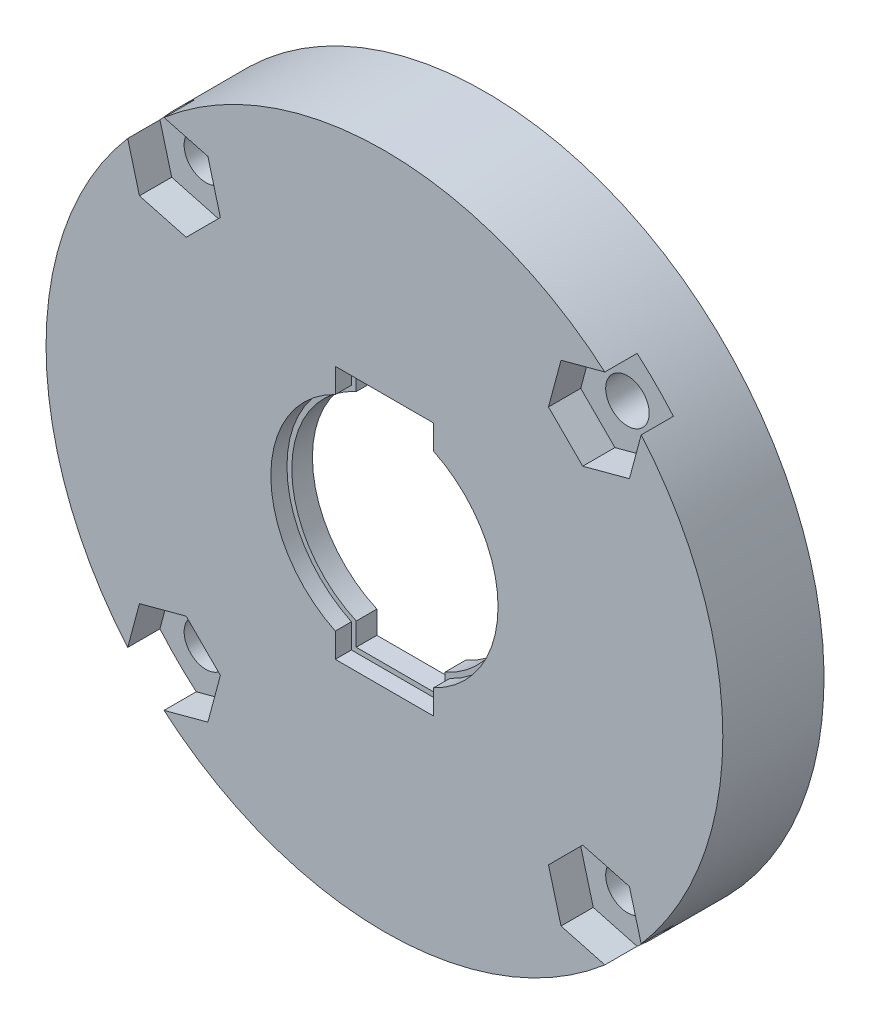
SolidWorks part; units mm, degrees
ref_plane "Front Plane" through (0, 0, 0) normal (0, 0, 1) x (1, 0, 0)
ref_plane "Top Plane" through (0, 0, 0) normal (0, 1, 0) x (1, 0, 0)
ref_plane "Right Plane" through (0, 0, 0) normal (1, 0, 0) x (0, 0, -1)
ref_axis "Z" through (0, 0, -0.1) along (0, 0, 1)
sketch "Sketch3" plane through (0, 0, 0) normal (0, 0, 1) x (1, 0, 0)
  line L132 (3.05, 6.3548) -> (3.05, 6.3561) construction
  line L133 (-3.05, 6.3561) -> (-3.05, 6.3548) construction
  line L134 (3.05, -6.3561) -> (3.05, -6.355) construction
  line L135 (-3.05, -6.355) -> (-3.05, -6.3561) construction
  line L198 (3.05, 6.3548) -> (3.05, 7.8744)
  line L199 (3.05, 7.8744) -> (-3.05, 7.8744)
  line L200 (-3.05, 7.8744) -> (-3.05, 6.3548)
  line L201 (-3.05, 6.3548) -> (-3.4914, 6.1247)
  line L202 (-3.4914, 6.1247) -> (-3.9416, 5.8451)
  line L203 (-3.9416, 5.8451) -> (-4.3696, 5.5325)
  line L204 (-4.3696, 5.5325) -> (-4.7729, 5.1886)
  line L205 (-4.7729, 5.1886) -> (-5.1492, 4.8154)
  line L206 (-5.1492, 4.8154) -> (-5.4964, 4.4149)
  line L207 (-5.4964, 4.4149) -> (-5.8125, 3.9896)
  line L208 (-5.8125, 3.9896) -> (-6.0958, 3.5417)
  line L209 (-6.0958, 3.5417) -> (-6.3446, 3.0737)
  line L210 (-6.3446, 3.0737) -> (-6.5576, 2.5884)
  line L211 (-6.5576, 2.5884) -> (-6.7335, 2.0885)
  line L212 (-6.7335, 2.0885) -> (-6.8714, 1.5768)
  line L213 (-6.8714, 1.5768) -> (-6.9705, 1.0561)
  line L214 (-6.9705, 1.0561) -> (-7.0301, 0.5295)
  line L215 (-7.0301, 0.5295) -> (-7.05, -0.0001)
  line L216 (-7.05, -0.0001) -> (-7.0301, -0.5297)
  line L217 (-7.0301, -0.5297) -> (-6.9705, -1.0563)
  line L218 (-6.9705, -1.0563) -> (-6.8714, -1.577)
  line L219 (-6.8714, -1.577) -> (-6.7335, -2.0887)
  line L220 (-6.7335, -2.0887) -> (-6.5576, -2.5887)
  line L221 (-6.5576, -2.5887) -> (-6.3446, -3.074)
  line L222 (-6.3446, -3.074) -> (-6.0958, -3.5419)
  line L223 (-6.0958, -3.5419) -> (-5.8125, -3.9898)
  line L224 (-5.8125, -3.9898) -> (-5.4964, -4.4152)
  line L225 (-5.4964, -4.4152) -> (-5.1492, -4.8156)
  line L226 (-5.1492, -4.8156) -> (-4.7729, -5.1888)
  line L227 (-4.7729, -5.1888) -> (-4.3696, -5.5327)
  line L228 (-4.3696, -5.5327) -> (-3.9416, -5.8453)
  line L229 (-3.9416, -5.8453) -> (-3.4914, -6.1249)
  line L230 (-3.4914, -6.1249) -> (-3.05, -6.355)
  line L231 (-3.05, -6.355) -> (-3.05, -7.8747)
  line L232 (-3.05, -7.8747) -> (3.05, -7.8747)
  line L233 (3.05, -7.8747) -> (3.05, -6.355)
  line L234 (3.05, -6.355) -> (3.4914, -6.1249)
  line L235 (3.4914, -6.1249) -> (3.9417, -5.8453)
  line L236 (3.9417, -5.8453) -> (4.3696, -5.5327)
  line L237 (4.3696, -5.5327) -> (4.7729, -5.1888)
  line L238 (4.7729, -5.1888) -> (5.1492, -4.8156)
  line L239 (5.1492, -4.8156) -> (5.4964, -4.4152)
  line L240 (5.4964, -4.4152) -> (5.8125, -3.9898)
  line L241 (5.8125, -3.9898) -> (6.0958, -3.5419)
  line L242 (6.0958, -3.5419) -> (6.3447, -3.074)
  line L243 (6.3447, -3.074) -> (6.5576, -2.5887)
  line L244 (6.5576, -2.5887) -> (6.7336, -2.0887)
  line L245 (6.7336, -2.0887) -> (6.8714, -1.577)
  line L246 (6.8714, -1.577) -> (6.9705, -1.0563)
  line L247 (6.9705, -1.0563) -> (7.0301, -0.5297)
  line L248 (7.0301, -0.5297) -> (7.05, -0.0001)
  line L249 (7.05, -0.0001) -> (7.0301, 0.5295)
  line L250 (7.0301, 0.5295) -> (6.9705, 1.0561)
  line L251 (6.9705, 1.0561) -> (6.8714, 1.5768)
  line L252 (6.8714, 1.5768) -> (6.7336, 2.0885)
  line L253 (6.7336, 2.0885) -> (6.5576, 2.5884)
  line L254 (6.5576, 2.5884) -> (6.3447, 3.0737)
  line L255 (6.3447, 3.0737) -> (6.0958, 3.5417)
  line L256 (6.0958, 3.5417) -> (5.8125, 3.9896)
  line L257 (5.8125, 3.9896) -> (5.4964, 4.4149)
  line L258 (5.4964, 4.4149) -> (5.1492, 4.8154)
  line L259 (5.1492, 4.8154) -> (4.7729, 5.1886)
  line L260 (4.7729, 5.1886) -> (4.3696, 5.5325)
  line L261 (4.3696, 5.5325) -> (3.9417, 5.8451)
  line L262 (3.9417, 5.8451) -> (3.4914, 6.1247)
  line L263 (3.4914, 6.1247) -> (3.05, 6.3548)
  line L264 (3.05, 6.3561) -> (3.05, 7.8744)
  line L265 (3.05, 7.8744) -> (-3.05, 7.8744)
  line L266 (-3.05, 7.8744) -> (-3.05, 6.3561)
  line L297 (-3.05, -6.3561) -> (-3.05, -7.8747)
  line L298 (-3.05, -7.8747) -> (3.05, -7.8747)
  line L299 (3.05, -7.8747) -> (3.05, -6.3561)
  arc A1 (-3.05, 6.3561) -> (-3.05, -6.3561) centre (0, 0) ccw
  arc A2 (3.05, 6.3561) -> (-3.05, 6.3561) centre (0, 0) ccw construction
  arc A3 (3.05, -6.3561) -> (3.05, 6.3561) centre (0, 0) ccw
  arc A4 (-3.05, -6.3561) -> (3.05, -6.3561) centre (0, 0) ccw construction
  circle A5 centre (0, 0) radius 21
  dimension "D1" = 14.1
  dimension "D3" = 42
  dimension "D2" = 0.05
extrude "Boss-Extrude2" add sketch "Sketch3" against normal blind 1
sketch "Sketch4" plane through (0, 0, -1) normal (0, 0, -1) x (-1, 0, 0)
  line L33 (2.75, 6.1644) -> (2.75, 7.5744)
  line L34 (2.75, 7.5744) -> (-2.75, 7.5744)
  line L35 (-2.75, 7.5744) -> (-2.75, 6.1644)
  line L36 (-2.75, -6.1644) -> (-2.75, -7.5747)
  line L37 (-2.75, -7.5747) -> (2.75, -7.5747)
  line L38 (2.75, -7.5747) -> (2.75, -6.1644)
  line L39 (2.75, 6.1644) -> (2.75, 7.5744)
  line L40 (2.75, 7.5744) -> (-2.75, 7.5744)
  line L41 (-2.75, 7.5744) -> (-2.75, 6.1644)
  line L42 (-2.75, -6.1644) -> (-2.75, -7.5747)
  line L43 (-2.75, -7.5747) -> (2.75, -7.5747)
  line L44 (2.75, -7.5747) -> (2.75, -6.1644)
  circle A13 centre (0, 0) radius 21 construction
  circle A14 centre (0, 0) radius 21
  arc A15 (-2.75, 6.1644) -> (-2.75, -6.1644) centre (0, 0) ccw
  arc A16 (2.75, -6.1644) -> (2.75, 6.1644) centre (0, 0) ccw
  arc A17 (-2.75, 6.1644) -> (-2.75, -6.1644) centre (0, 0) ccw
  arc A18 (2.75, -6.1644) -> (2.75, 6.1644) centre (0, 0) ccw
  dimension "D1" = 0.3
extrude "Boss-Extrude3" add sketch "Sketch4" along normal blind 5.28
sketch "Sketch5" plane through (0, 0, -6.28) normal (0, 0, -1) x (-1, 0, 0)
  circle A0 centre (0, 0) radius 16.5
  dimension "D1" = 33
extrude "Cut-Extrude1" cut sketch "Sketch5" against normal blind 4
sketch "Sketch6" plane through (0, 0, 0) normal (0, 0, 1) x (1, 0, 0)
  line L0 (0, 0) -> (13.0815, 13.0815) construction
  line L1 (-16.3801, 0) -> (0, 0) construction
  line L3 (13.8585, 15.9814) -> (10.9586, 15.2044)
  line L4 (10.9586, 15.2044) -> (10.1816, 12.3044)
  line L5 (10.1816, 12.3044) -> (12.3044, 10.1816)
  line L6 (12.3044, 10.1816) -> (15.2044, 10.9586)
  line L7 (15.2044, 10.9586) -> (15.9814, 13.8585)
  line L8 (15.9814, 13.8585) -> (13.8585, 15.9814)
  circle A0 centre (13.0815, 13.0815) radius 2.6 construction
  dimension "D3" = 5.2
  dimension "D1" = 135
  dimension "D2" = 18.5
extrude "Cut-Extrude2" cut sketch "Sketch6" against normal blind 2
sketch "Sketch8" plane through (0, 0, 0) normal (0, 0, 1) x (1, 0, 0)
  line L0 (36.6653, 0) -> (49.0214, 0) construction
  line L1 (0, 0) -> (13.0815, 13.0815) construction
  circle A0 centre (0, 0) radius 18.5 construction
  circle A1 centre (13.0815, 13.0815) radius 1.35
  dimension "D1" = 37
  dimension "D3" = 2.7
  dimension "D2" = 135
extrude "Cut-Extrude4" cut sketch "Sketch8" against normal through all
pattern_circular "CirPattern1" count 4 over 360 about axis through (0, 0, -0.1) along (0, 0, 1) of "Cut-Extrude2", "Cut-Extrude4"
ref_plane "Plane4" through (0, 0, 0) normal (-0.7071, 0.7071, 0) x (0, 0, 1)
